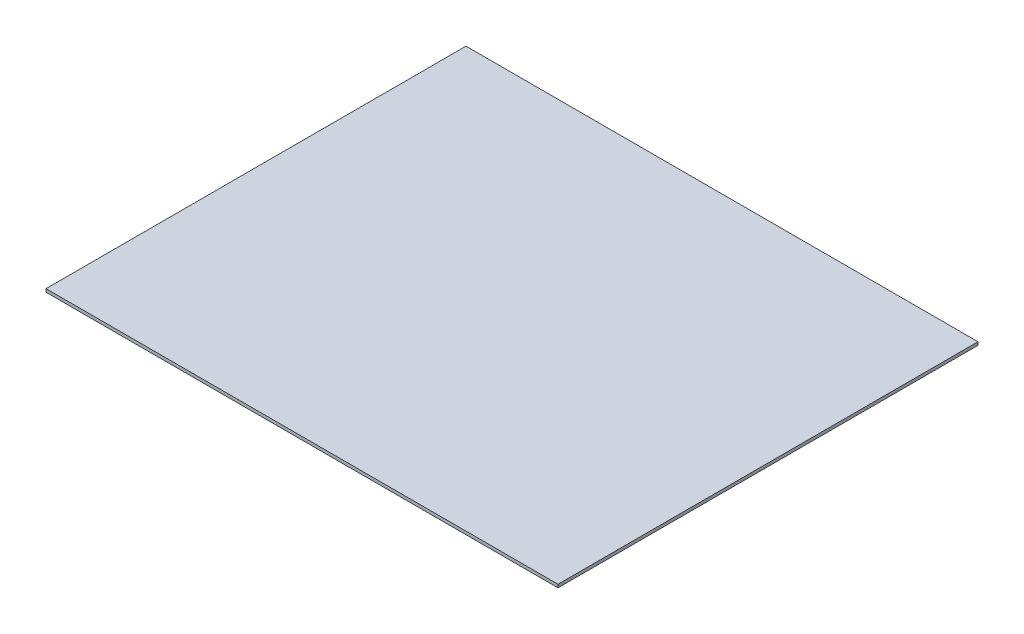
SolidWorks part; units mm, degrees
material "PVC 0.007 Plasticized"
ref_plane "Front Plane" through (0, 0, 0) normal (0, 0, 1) x (1, 0, 0)
ref_plane "Top Plane" through (0, 0, 0) normal (0, 1, 0) x (1, 0, 0)
ref_plane "Right Plane" through (0, 0, 0) normal (1, 0, 0) x (0, 0, -1)
sketch "Sketch1" plane through (0, 0, 0) normal (0, 1, 0) x (1, 0, 0)
  line L1 (-187.325, -153.67) -> (187.325, -153.67)
  line L2 (-187.325, -153.67) -> (-187.325, 153.67)
  line L3 (-187.325, 153.67) -> (187.325, 153.67)
  line L4 (187.325, -153.67) -> (187.325, 153.67)
  line L5 (-187.325, -153.67) -> (187.325, 153.67) construction
  line L6 (-187.325, 153.67) -> (187.325, -153.67) construction
  point P0 (0, 0)
  dimension "D1" = 307.34
  dimension "D2" = 374.65
extrude "Boss-Extrude1" add sketch "Sketch1" along normal blind 2.286
